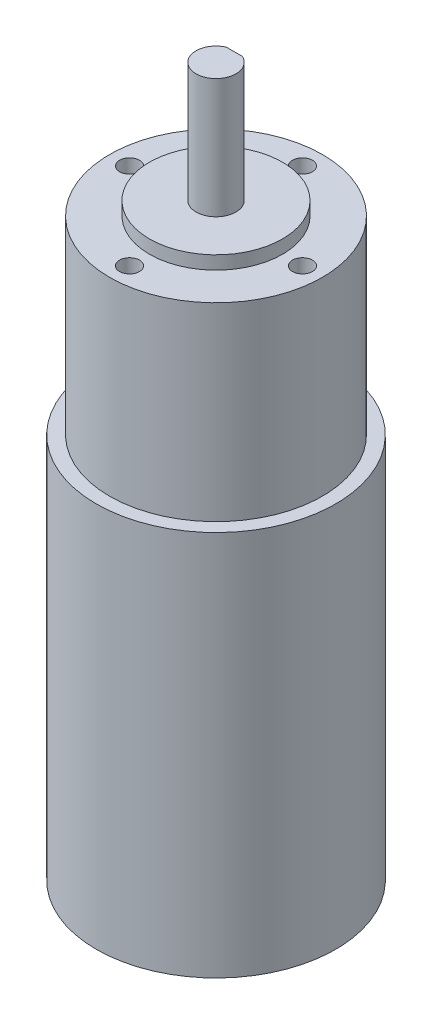
SolidWorks part; units mm, degrees
ref_plane "Plan de face" through (0, 0, 0) normal (0, 0, 1) x (1, 0, 0)
ref_plane "Plan de dessus" through (0, 0, 0) normal (0, 1, 0) x (1, 0, 0)
ref_plane "Plan de droite" through (0, 0, 0) normal (1, 0, 0) x (0, 0, -1)
sketch "Esquisse1" plane through (0, 0, 0) normal (0, 1, 0) x (1, 0, 0)
  circle A0 centre (0, 0) radius 18
  dimension "D1" = 36
extrude "Boss.-Extru.1" add sketch "Esquisse1" along normal blind 86.5
sketch "Esquisse2" plane through (0, 86.5, 0) normal (0, 1, 0) x (1, 0, 0)
  circle A0 centre (0, 0) radius 10
  dimension "D1" = 20
extrude "Boss.-Extru.2" add sketch "Esquisse2" along normal blind 2
sketch "Esquisse3" plane through (0, 88.5, 0) normal (0, 1, 0) x (1, 0, 0)
  circle A0 centre (0, 0) radius 3
  dimension "D1" = 6
extrude "Boss.-Extru.3" add sketch "Esquisse3" along normal blind 18
sketch "Esquisse4" plane through (0, 106.5, 0) normal (0, 1, 0) x (1, 0, 0)
  line L0 (0, 0) -> (0, 1.9338) construction
  line L1 (-1.199, 2.75) -> (1.199, 2.75)
  circle A0 centre (0, 0) radius 3 construction
  circle A1 centre (0, 0) radius 3 construction
  circle A2 centre (0, 0) radius 2.75
  circle A3 centre (0, 0) radius 3
  circle A4 centre (0, 0) radius 3
  point P10 (0, 3)
  circle M4 centre (0, 0) radius 3
  dimension "D1" = 5.5
  dimension "D2" = 0
extrude "Enlèv. mat.-Extru.1" cut sketch "Esquisse4" against normal blind 15 contours L0 L1 M4 | L1 L0 A4 region at (0, 106.5, -2.8504)
sketch "Esquisse6" plane through (0, 86.5, 0) normal (0, 1, 0) x (1, 0, 0)
  line L0 (0, 0) -> (12.7884, 0) construction
  line L1 (0, 0) -> (13, 0) construction
  circle A0 centre (13, 0) radius 1.5
  dimension "D3" = 3
  dimension "D2" = 13
extrude "Enlèv. mat.-Extru.2" cut sketch "Esquisse6" against normal blind 10
ref_axis "Rev" through (0, -10.575, 0) along (0, 1, 0)
pattern_circular "Répétition circulaire1" count 4 over 360 about axis through (0, -10.575, 0) along (0, 1, 0) of "Enlèv. mat.-Extru.2"
sketch "Esquisse7" plane through (0, 86.5, 0) normal (0, 1, 0) x (1, 0, 0)
  circle A0 centre (0, 0) radius 16
  circle A2 centre (0, 0) radius 18 construction
  circle A3 centre (0, 0) radius 18
  dimension "D1" = 32
extrude "Enlèv. mat.-Extru.3" cut sketch "Esquisse7" against normal blind 28.5
